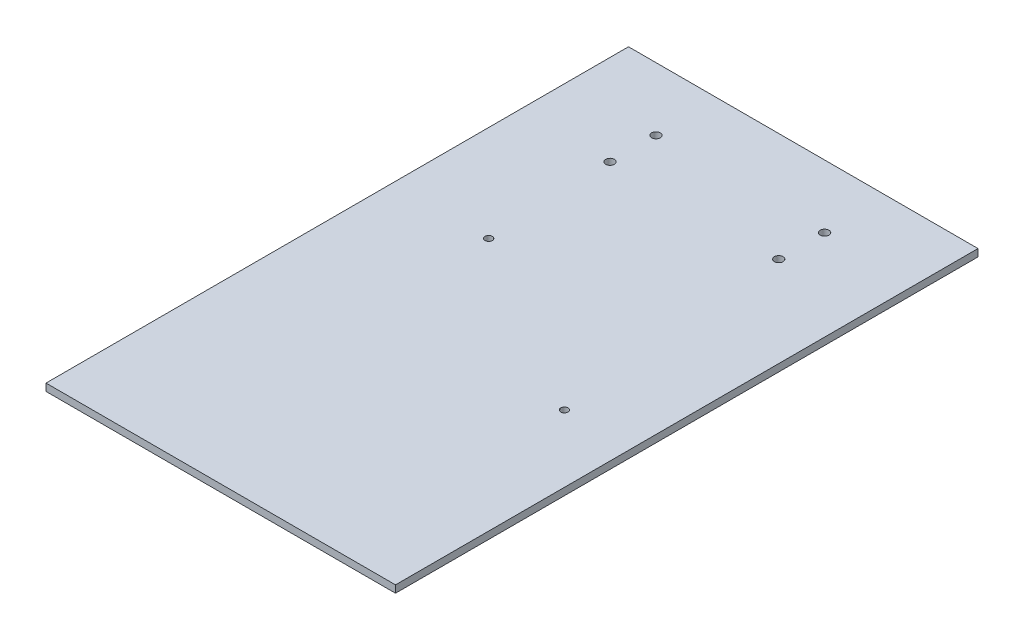
SolidWorks part; units mm, degrees
ref_plane "Front Plane" through (0, 0, 0) normal (0, 0, 1) x (1, 0, 0)
ref_plane "Top Plane" through (0, 0, 0) normal (0, 1, 0) x (1, 0, 0)
ref_plane "Right Plane" through (0, 0, 0) normal (1, 0, 0) x (0, 0, -1)
sketch "Sketch1" plane through (0, 0, 0) normal (0, 1, 0) x (1, 0, 0)
  line L1 (-76.2, -127) -> (76.2, -127)
  line L2 (-76.2, -127) -> (-76.2, 127)
  line L3 (-76.2, 127) -> (76.2, 127)
  line L4 (76.2, -127) -> (76.2, 127)
  line L5 (-76.2, -127) -> (76.2, 127) construction
  line L6 (-76.2, 127) -> (76.2, -127) construction
  point P0 (0, 0)
  dimension "D1" = 254
  dimension "D2" = 152.4
extrude "Boss-Extrude1" add sketch "Sketch1" along normal blind 3.175
sketch "Sketch4" plane through (0, 3.175, 0) normal (0, 1, 0) x (1, 0, 0)
  circle A0 centre (-34.29, 24.13) radius 1.5875
  circle A1 centre (46.99, -24.13) radius 1.5875
  dimension "D5" = 3.175
  dimension "D6" = 3.175
  dimension "D1" = 24.13
  dimension "D2" = 34.29
  dimension "D3" = 81.28
  dimension "D4" = 48.26
extrude "Cut-Extrude1" cut sketch "Sketch4" against normal through all
hole_wizard "#6 Clearance Hole1" positions "Sketch8" profile "Sketch7" hole size "#6" standard "ANSI Inch" end condition through all
sketch "Sketch8" plane through (0, 3.175, 0) normal (0, 1, 0) x (1, 0, 0)
  line L0 (-76.2, 127) -> (-76.2, -127) construction
  line L1 (76.2, 127) -> (-76.2, 127) construction
  line L2 (76.2, -127) -> (76.2, 127) construction
  point P0 (-36.77, 99.54)
  point P2 (-36.77, 79.54)
  point P4 (36.77, 99.54)
  point P6 (36.77, 79.54)
  dimension "D1" = 39.43
  dimension "D2" = 27.46
  dimension "D3" = 20
  dimension "D4" = 39.43
  dimension "D5" = 20
sketch "Sketch7" plane through (-36.77, 3.175, -99.54) normal (1, 0, 0) x (0, 0, 1)
  line L0 (0, 0) -> (0, 3.175)
  line L1 (0, 3.175) -> (1.8986, 3.175)
  line L2 (1.8986, 3.175) -> (1.8986, 0)
  line L5 (1.8986, 0) -> (0, 0)
  line L11 (0, -6.35) -> (0, 107.95) construction
  dimension "Thru Hole Dia." = 3.7973
  dimension "Thru Hole Depth" = 3.175
equation "\"R_megaHole\"= 0.125in"
equation "\"X_megaHoleDist\"= 3.2in'Hole distances from each other"
equation "\"Z_megaHoleDist\"= 1.9in"
equation "\"X_megaHoleO\"= 1.35in'Hole 1 distance from origin"
equation "\"Z_megaHoleO\"= 0.95in"
equation "\"D2@Sketch4\"= \"X_megaHoleO\""
equation "\"D1@Sketch4\"= \"Z_megaHoleO\""
equation "\"D3@Sketch4\"= \"X_megaHoleDist\""
equation "\"D4@Sketch4\"= \"Z_megaHoleDist\""
equation "\"D6@Sketch4\"= \"R_megaHole\""
equation "\"D5@Sketch4\"= \"R_megaHole\""
